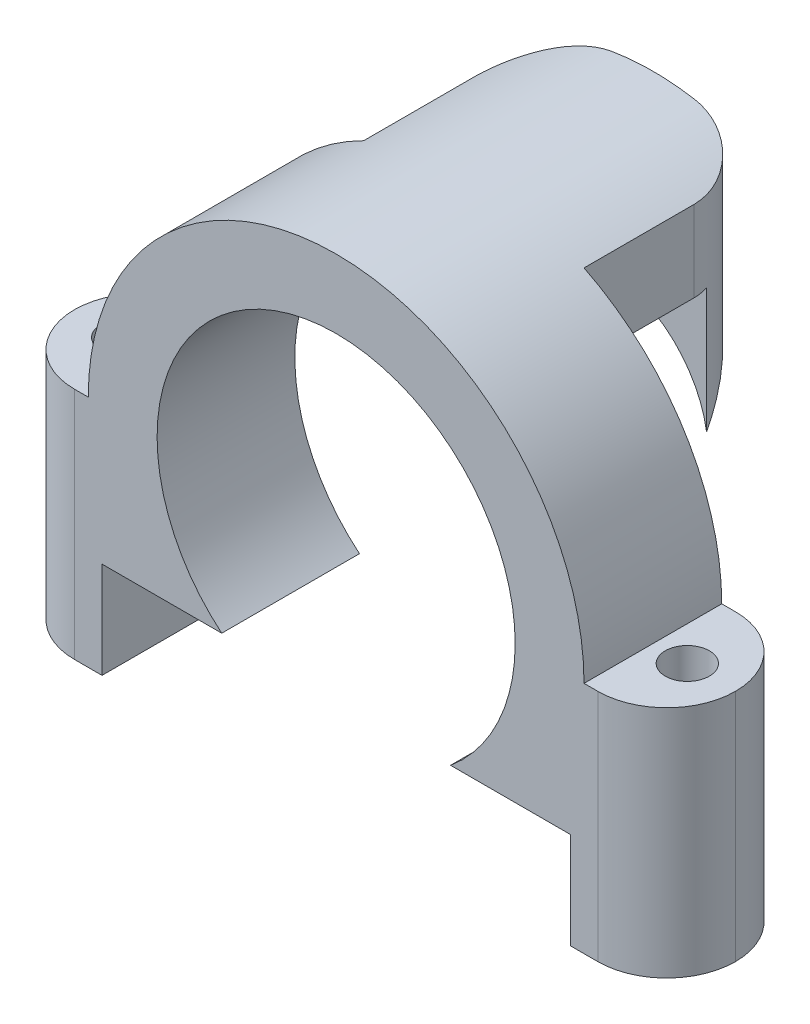
SolidWorks part; units mm, degrees
ref_plane "Front Plane" through (0, 0, 0) normal (0, 0, 1) x (1, 0, 0)
ref_plane "Top Plane" through (0, 0, 0) normal (0, 1, 0) x (1, 0, 0)
ref_plane "Right Plane" through (0, 0, 0) normal (1, 0, 0) x (0, 0, -1)
sketch "Sketch1" plane through (0, 0, 0) normal (0, 0, 1) x (1, 0, 0)
  line L0 (-18, 0) -> (-24, 0)
  line L1 (-24, 0) -> (-24, -10)
  line L2 (18, 0) -> (24, 0)
  line L3 (24, 0) -> (24, -10)
  line L4 (-24, -10) -> (24, -10)
  arc A0 (18, 0) -> (-18, 0) centre (0, 0) ccw
  circle A1 centre (0, 0) radius 6
  dimension "D5" = 12
  dimension "D7" = 36
  dimension "D1" = 10
  dimension "D2" = 24
  dimension "D4" = 24
extrude "Extrude1" add sketch "Sketch1" along normal blind 10
sketch "Sketch2" plane through (0, 0, 0) normal (0, 0, -1) x (-1, 0, 0)
  circle A0 centre (0, 0) radius 13
  dimension "D1" = 26
extrude "Cut-Extrude1" cut sketch "Sketch2" against normal blind 6
sketch "Sketch3" plane through (0, 0, 0) normal (0, 1, 0) x (-1, 0, 0)
  line L0 (-24, 10) -> (-24, 0) construction
  line L1 (-24, 10) -> (-18, 10) construction
  line L3 (24, 10) -> (24, 0) construction
  line L4 (18, 10) -> (24, 10) construction
  circle A0 centre (-20.5, 5) radius 1.6
  circle A1 centre (20.5, 5) radius 1.6
  dimension "D1" = 3.2
  dimension "D3" = 5
  dimension "D4" = 3.2
  dimension "D5" = 3.5
  dimension "D6" = 5
  dimension "D2" = 3.5
extrude "Cut-Extrude2" cut sketch "Sketch3" against normal up to surface (10 mm away) up to face at (0, -10, 4)
sketch "Sketch4" plane through (0, -10, 0) normal (0, -1, 0) x (1, 0, 0)
  line L0 (-24, 10) -> (-17, 10)
  line L1 (-24, 10) -> (24, 10) construction
  line L2 (-17, 10) -> (-17, 0)
  line L3 (-24, 0) -> (-8.3066, 0) construction
  line L4 (-17, 0) -> (-24, 0)
  line L5 (-24, 0) -> (-24, 10)
  line L6 (-24, 10) -> (-23.8414, 9.8046)
  line L7 (24, 10) -> (24, 0)
  line L8 (24, 0) -> (17, 0)
  line L9 (8.3066, 0) -> (24, 0) construction
  line L10 (17, 0) -> (17, 10)
  line L11 (17, 10) -> (24, 10)
  dimension "D1" = 7
  dimension "D2" = 7
extrude "Extrude3" add sketch "Sketch4" along normal blind 7
fillet "Fillet2" radius 5 4 edges at (24, -8.5, 10) (24, -8.5, 0) (-24, -8.5, 10) (-24, -8.5, 0)
sketch "Sketch5" plane through (0, 0, 6) normal (0, 0, -1) x (-1, 0, 0)
  circle A0 centre (0, 0) radius 13
extrude "Extrude4" cut sketch "Sketch5" against normal up to surface (4 mm away) up to face at (0, -7, 10)
sketch "Sketch6" plane through (0, 0, 0) normal (0, 0, -1) x (-1, 0, 0)
  line L0 (-8, 10.247) -> (-8, 16.1245)
  line L1 (8, 10.247) -> (8, 16.1245)
  arc A0 (8, 10.247) -> (-8, 10.247) centre (0, 0) ccw
  arc A1 (8.3066, -10) -> (-8.3066, -10) centre (0, 0) ccw construction
  arc A2 (18, 0) -> (-18, 0) centre (0, 0) ccw construction
  arc A3 (8, 16.1245) -> (-8, 16.1245) centre (0, 0) ccw
  dimension "D1" = 8
  dimension "D2" = 8
extrude "Extrude5" add sketch "Sketch6" along normal blind 9
sketch "Sketch7" plane through (0, 0, -9) normal (0, 0, -1) x (-1, 0, 0)
  line L0 (8, 16.1245) -> (8, 0)
  line L1 (-8, 16.1245) -> (-8, 0)
  arc A0 (-8, 16.1245) -> (8, 16.1245) centre (0, 0) cw
  arc A1 (18, 0) -> (8, 16.1245) centre (0, 0) ccw construction
  arc A2 (8, 0) -> (-8, 0) centre (0, 0) ccw
  dimension "D1" = 8
extrude "Extrude6" add sketch "Sketch7" along normal blind 4
fillet "Fillet3" radius 5 2 edges at (-8, 8.0623, -13) (8, 8.0623, -13)
hole_wizard "M4 Tapped Hole1" positions "3DSketch1" profile "Sketch9" tap size "M4" standard "DIN"
sketch3d "3DSketch1"
  line L0 (-20.5, -17, 5) -> (-20.5, 0, 5) construction
  line L1 (20.5, -17, 5) -> (20.5, 0, 5) construction
  point P0 (-20.5, -17, 5)
  point P4 (20.5, -17, 5)
sketch "Sketch9" plane through (-20.5, -17, 5) normal (1, 0, 0) x (0, 0, -1)
  line L0 (0, 0) -> (0, 11.0914)
  line L1 (0, 11.0914) -> (1.65, 10.1)
  line L2 (1.65, 10.1) -> (1.65, 0)
  line L5 (1.65, 0) -> (0, 0)
  line L10 (0, 11.0914) -> (-1.65, 10.1) construction
  line L11 (0, -6.35) -> (0, 107.95) construction
  dimension "Tap Drill Dia." = 3.3
  dimension "Tap Drill Depth" = 10.1
  dimension "Drill Angle" = 118
cosmetic thread "Hole Thread1" parameters "D1"=8, "D2"=4
cosmetic thread "Hole Thread2" parameters "D1"=8, "D2"=4
